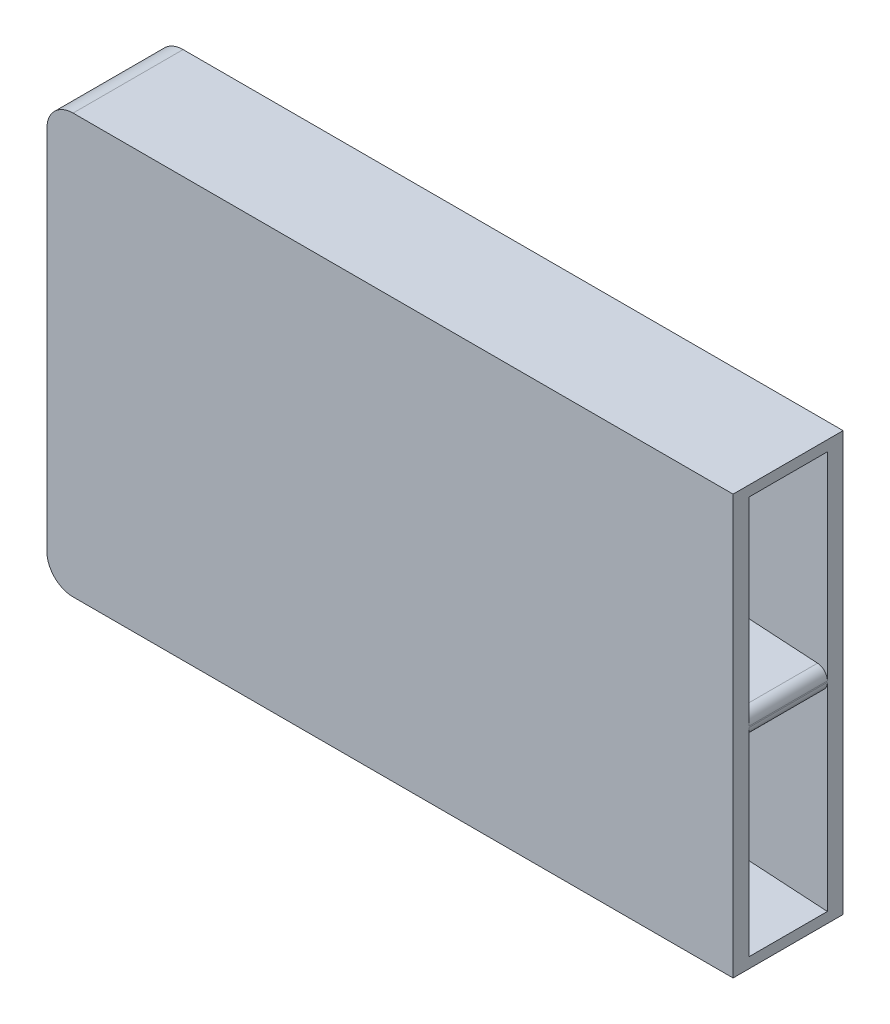
SolidWorks part; units mm, degrees
material "ABS"
ref_plane "Front Plane" through (0, 0, 0) normal (0, 0, 1) x (1, 0, 0)
ref_plane "Top Plane" through (0, 0, 0) normal (0, 1, 0) x (1, 0, 0)
ref_plane "Right Plane" through (0, 0, 0) normal (1, 0, 0) x (0, 0, -1)
sketch "Sketch1" plane through (0, 0, 0) normal (0, 0, 1) x (1, 0, 0)
  line L0 (0, 0) -> (0, 40)
  line L1 (0, 40) -> (65.5, 40)
  line L2 (65.5, 40) -> (65.5, 0)
  line L3 (65.5, 0) -> (0, 0)
  line L4 (65.5, 20) -> (0, 20) construction
  line L5 (0, 5) -> (65.5, 1)
  line L6 (0, 15) -> (65.5, 19)
  line L7 (0, 10) -> (65.5, 10) construction
  line L8 (0, 35) -> (65.5, 39)
  line L9 (0, 30) -> (65.5, 30) construction
  line L10 (0, 25) -> (65.5, 21)
  dimension "D1" = 40
  dimension "D2" = 10
  dimension "D3" = 18
  dimension "D4" = 20
  dimension "D5" = 65.5
extrude "Boss-Extrude1" add sketch "Sketch1" against normal blind 1.5 contours L0 L8 L2 L1 | L0 L10 L2 L8 | L10 L0 L6 L2 | L6 L0 L5 L2 | L5 L0 L3 L2 region at (25.4722, 1.7222, 0) region at (35.869, 10, 0) region at (25.4722, 20, 0) region at (35.869, 30, 0) region at (25.4722, 38.2778, 0)
extrude "Boss-Extrude2" add sketch "Sketch1<3>" along normal blind 7.5 contours L0 L8 L2 L1 | L10 L0 L6 L2 | L5 L0 L3 L2 region at (25.4722, 1.7222, 0) region at (25.4722, 20, 0) region at (25.4722, 38.2778, 0)
sketch "Sketch1<3>" plane through (0, 0, 0) normal (0, 0, 1) x (1, 0, 0) same geometry as "Sketch1"
extrude "Boss-Extrude3" add sketch "Sketch1<5>" along normal blind 1.5 from offset 7.5 contours L0 L8 L2 L1 | L0 L10 L2 L8 | L10 L0 L6 L2 | L6 L0 L5 L2 | L5 L0 L3 L2 region at (25.4722, 1.7222, 0) region at (35.869, 10, 0) region at (25.4722, 20, 0) region at (35.869, 30, 0) region at (25.4722, 38.2778, 0)
sketch "Sketch1<5>" plane through (0, 0, 0) normal (0, 0, 1) x (1, 0, 0) same geometry as "Sketch1"
fillet "Fillet1" radius 2.5 2 edges at (0, 40, 3.75) (0, 0, 3.75)
fillet "Fillet2" radius 1 2 edges at (65.5, 21, 3.75) (65.5, 19, 3.75)
